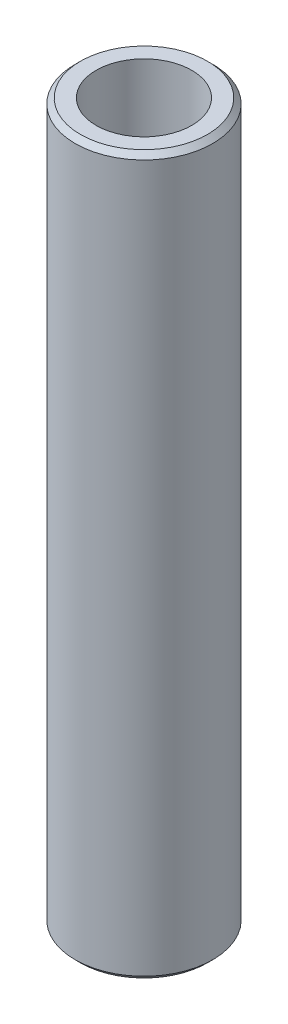
SolidWorks part; units mm, degrees
ref_plane "Front Plane" through (0, 0, 0) normal (0, 0, 1) x (1, 0, 0)
ref_plane "Top Plane" through (0, 0, 0) normal (0, 1, 0) x (1, 0, 0)
ref_plane "Right Plane" through (0, 0, 0) normal (1, 0, 0) x (0, 0, -1)
sketch "Sketch1" plane through (0, 0, 0) normal (0, 1, 0) x (1, 0, 0)
  circle A0 centre (0, 0) radius 57.5
  dimension "SHAFT_OD" = 115
extrude "Boss-Extrude1" add sketch "Sketch1" along normal blind 600
sketch "Sketch2" plane through (0, 0, 0) normal (0, 1, 0) x (1, 0, 0)
  circle A0 centre (0, 0) radius 39.9863
  dimension "BORE_D" = 79.9726
extrude "Cut-Extrude1" cut sketch "Sketch2" along normal through all
chamfer "Chamfer1" distance 4.385 angle 45 2 edges at (0, 600, 57.5) (0, 0, 57.5)
